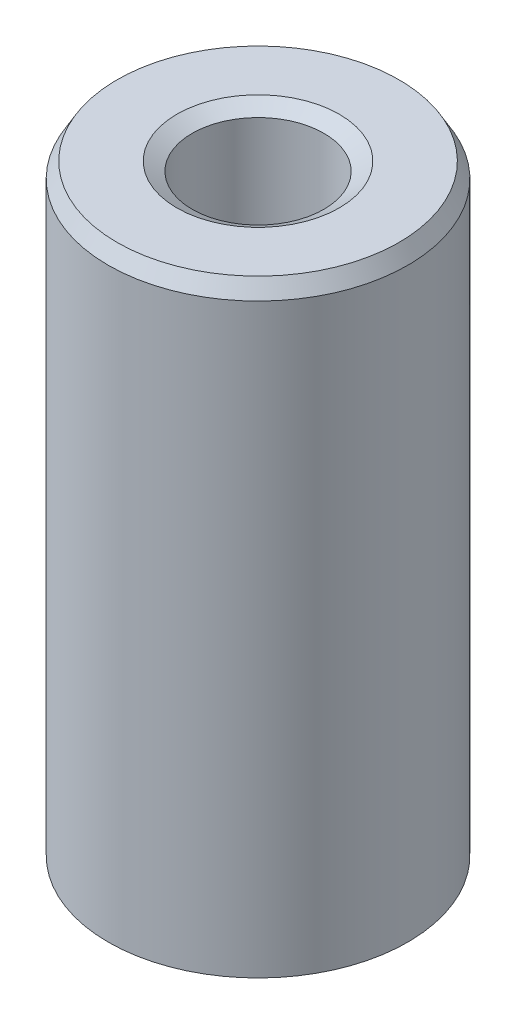
SolidWorks part; units mm, degrees
ref_plane "Front Plane" through (0, 0, 0) normal (0, 0, 1) x (1, 0, 0)
ref_plane "Top Plane" through (0, 0, 0) normal (0, 1, 0) x (1, 0, 0)
ref_plane "Right Plane" through (0, 0, 0) normal (1, 0, 0) x (0, 0, -1)
sketch "Sketch1" plane through (0, 0, 0) normal (0, 1, 0) x (1, 0, 0)
  circle A0 centre (0, 0) radius 17.5
  dimension "SLEEVE_OD" = 35
extrude "Boss-Extrude1" add sketch "Sketch1" along normal blind 71.3074
sketch "Sketch2" plane through (0, 0, 0) normal (0, 1, 0) x (1, 0, 0)
  circle A0 centre (0, 0) radius 7.6956
  dimension "BORE_D" = 15.3913
extrude "Cut-Extrude1" cut sketch "Sketch2" along normal through all
chamfer "Chamfer1" distance 1.7911 angle 30 4 edges at (0, 71.3074, 7.6956) (0, 0, 7.6956) (0, 0, 17.5) (0, 71.3074, 17.5) first distance on face at (0, 71.3074, 7.6956) first distance on face at (0, 0, 7.6956) first distance on face at (0, 71.3074, 17.5)
